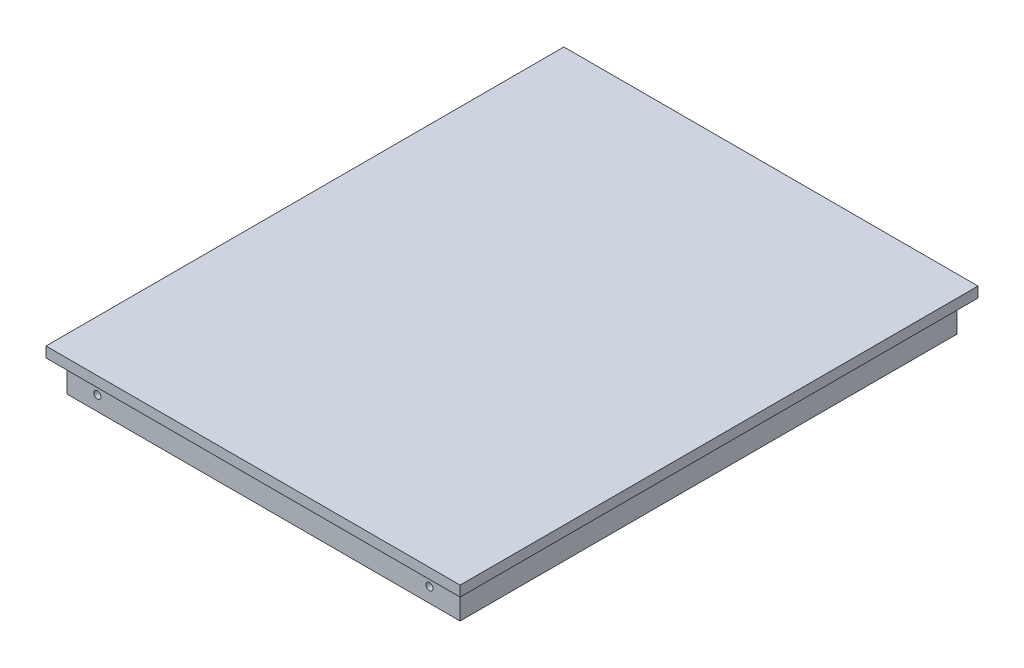
SolidWorks part; units mm, degrees
material "PLA 15%"
ref_plane "Front Plane" through (0, 0, 0) normal (0, 0, 1) x (1, 0, 0)
ref_plane "Top Plane" through (0, 0, 0) normal (0, 1, 0) x (1, 0, 0)
ref_plane "Right Plane" through (0, 0, 0) normal (1, 0, 0) x (0, 0, -1)
sketch "Sketch1" plane through (0, 0, 0) normal (0, 1, 0) x (1, 0, 0)
  line L0 (-94.75, 119.75) -> (94.75, 119.75)
  line L1 (94.75, 119.75) -> (94.75, -119.75)
  line L2 (94.75, -119.75) -> (-94.75, -119.75)
  line L3 (-94.75, -119.75) -> (-94.75, 119.75)
  line L4 (-94.75, 119.75) -> (94.75, 119.75)
  line L5 (-94.75, 119.75) -> (94.75, -119.75) construction
  line L6 (-89.75, 114.75) -> (89.75, 114.75)
  line L7 (89.75, 114.75) -> (89.75, -114.75)
  line L8 (89.75, -114.75) -> (-89.75, -114.75)
  line L9 (-89.75, -114.75) -> (-89.75, 114.75)
  line L10 (-89.75, 114.75) -> (89.75, 114.75)
  line L11 (-94.75, 114.75) -> (94.75, 114.75) construction
  line L12 (-94.75, 114.75) -> (94.75, 114.75) construction
  line L13 (-89.75, -114.75) -> (-89.75, 119.75) construction
  line L14 (89.75, 119.75) -> (89.75, -114.75) construction
  line L15 (94.75, 119.75) -> (-94.75, -119.75) construction
  line L16 (-99.75, 124.75) -> (99.75, 124.75)
  line L17 (99.75, 124.75) -> (99.75, -124.75)
  line L18 (99.75, -124.75) -> (-99.75, -124.75)
  line L19 (-99.75, -124.75) -> (-99.75, 124.75)
  point P4 (0, 0)
  dimension "D1" = 189.5
  dimension "D2" = 239.5
  dimension "D4" = 5
  dimension "D5" = 5
  dimension "D6" = 5
  dimension "D7" = 5
  dimension "D3" = 5
extrude "Boss-Extrude1" add sketch "Sketch1" along normal blind 5 contours L3 L2 L1 L0 L8 L9 L6 L7 | L19 L18 L17 L16 L2 L3 L0 L1 | L9 L8 L7 L6 region at (0, 0, -116.696) region at (0, 0, 0) region at (0, 0, -121.5555)
extrude "Boss-Extrude2" add sketch "Sketch1<3>" against normal blind 15 contours L3 L2 L1 L0 L8 L9 L6 L7 region at (0, 0, -116.696)
sketch "Sketch1<3>" plane through (0, 0, 0) normal (0, 1, 0) x (1, 0, 0) same geometry as "Sketch1"
sketch "Sketch2" plane through (0, 0, 0) normal (0, 0, 1) x (1, 0, 0)
  line L0 (0, 0) -> (-80, 0) construction
  line L2 (0, 0) -> (0, -6.4593) construction
  line L4 (-80, -8) -> (-80, 0) construction
  circle A0 centre (-80, -8) radius 1.625
  circle A1 centre (80, -8) radius 1.625 construction
  point P0 (-80, -8)
  point P2 (80, -8)
  dimension "D1" = 3.25
  dimension "D2" = 80
  dimension "D3" = 8
hole_wizard "M3 Clearance Hole1" positions "Sketch2" profile "Sketch4" hole size "M3" standard "ANSI Metric" end condition through all
sketch "Sketch4" plane through (-80, -8, 0) normal (1, 0, 0) x (0, 1, 0)
  line L0 (0, 0) -> (0, 124.75)
  line L1 (0, 124.75) -> (1.7, 124.75)
  line L2 (1.7, 124.75) -> (1.7, 0.025)
  line L3 (1.7, 0.025) -> (1.725, 0)
  line L5 (1.725, 0) -> (0, 0)
  line L6 (-1.7, 0.025) -> (-1.725, 0) construction
  line L11 (0, -6.35) -> (0, 107.95) construction
  dimension "Thru Hole Dia." = 3.4
  dimension "Thru Hole Depth" = 124.75
  dimension "Near C'Sink Dia." = 3.45
  dimension "Near C'Sink Angle" = 90
mirror "Mirror1" about plane through (0, 0, 0) normal (0, 0, 1) of "M3 Clearance Hole1"
